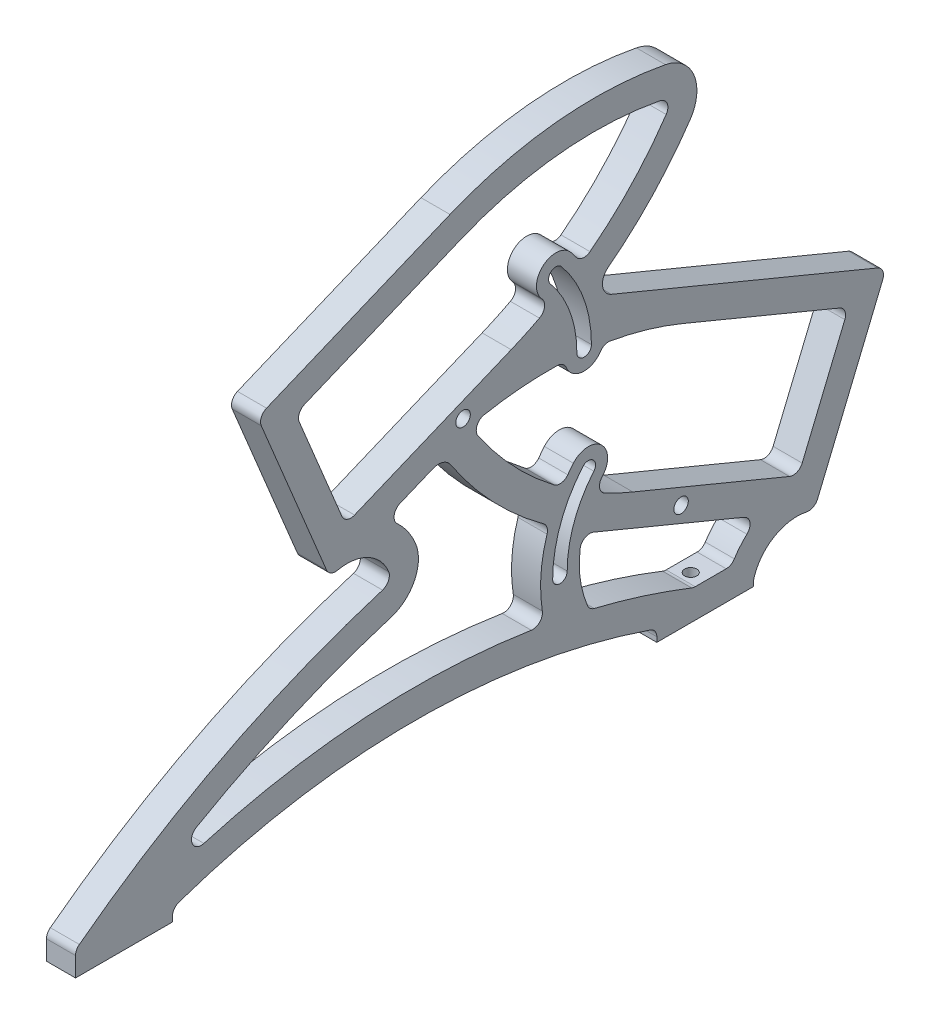
SolidWorks part; units mm, degrees
material "1060 Alloy"
ref_plane "Front Plane" through (0, 0, 0) normal (0, 0, 1) x (1, 0, 0)
ref_plane "Top Plane" through (0, 0, 0) normal (0, 1, 0) x (1, 0, 0)
ref_plane "Right Plane" through (0, 0, 0) normal (1, 0, 0) x (0, 0, -1)
sketch "Sketch1" plane through (0, 0, 0) normal (1, 0, 0) x (0, 0, -1)
  line L0 (0, 0) -> (0, 5)
  line L1 (38.8897, 80.8553) -> (54.5797, 42.9762) construction
  line L2 (38.8897, 80.8553) -> (112.8001, 111.47) construction
  line L3 (54.5797, 42.9762) -> (128.4901, 73.5909) construction
  line L4 (41.5028, 79.7729) -> (54.1314, 49.2849) construction
  line L5 (112.8001, 111.47) -> (128.4901, 73.5909) construction
  line L6 (20, 1) -> (20, 0)
  line L7 (0, 0) -> (20, 0)
  line L8 (54.1314, 49.2849) -> (91.0866, 64.5922) construction
  line L9 (78.458, 95.0802) -> (41.5028, 79.7729) construction
  line L10 (80, 60) -> (105, 60) construction
  line L11 (99.1511, 76.0697) -> (80, 60) construction
  line L12 (100, 22) -> (125, 22) construction
  line L13 (125, 22) -> (105.8489, 38.0697) construction
  line L14 (166.1103, 42.8553) -> (150.4203, 4.9762) construction
  line L15 (166.1103, 42.8553) -> (92.1999, 73.47) construction
  line L16 (150.4203, 4.9762) -> (76.5099, 35.5909) construction
  line L17 (92.1999, 73.47) -> (76.5099, 35.5909) construction
  line L18 (150.8686, 11.2849) -> (163.4972, 41.7729) construction
  line L19 (163.4972, 41.7729) -> (126.542, 57.0802) construction
  line L20 (113.9134, 26.5922) -> (150.8686, 11.2849) construction
  line L21 (157.1829, 26.5289) -> (85.1203, 56.3782) construction
  line L22 (47.8171, 64.5289) -> (119.8797, 94.3782) construction
  line L23 (152.4922, 7.3652) -> (167.4169, 43.3965)
  line L24 (167.4169, 43.3965) -> (110.6328, 66.9172)
  line L25 (77.31, 97.8519) -> (37.5831, 81.3965)
  line L26 (37.5831, 81.3965) -> (52.5078, 45.3652)
  line L27 (63.7245, 50.0113) -> (73.7782, 54.1757)
  line L28 (140, 0) -> (140, 1)
  line L29 (152.4922, 7.3652) -> (143.6238, 11.0386) construction
  line L30 (89.9385, 67.3638) -> (55.755, 53.2046)
  line L31 (55.755, 53.2046) -> (45.4225, 78.1493)
  line L32 (45.4225, 78.1493) -> (79.6061, 92.3086)
  line L33 (115.0615, 29.3638) -> (149.245, 15.2046)
  line L34 (149.245, 15.2046) -> (159.5775, 40.1493)
  line L35 (159.5775, 40.1493) -> (125.3939, 54.3086)
  line L36 (56.0604, 36.7884) -> (62.7895, 39.5756) construction
  line L37 (52.5078, 45.3652) -> (58.8317, 47.9846) construction
  line L38 (104.6495, 27.1823) -> (141.2755, 12.0113)
  line L39 (135.4645, 6) -> (127.5413, 6)
  line L43 (140, 0) -> (120, 0)
  line L56 (120, 1) -> (120, 0)
  line L63 (174.6584, 100) -> (-14.1241, 100) construction
  circle A0 centre (80, 60) radius 1.5
  circle A1 centre (125, 22) radius 1.5
  arc A2 (99.1511, 76.0697) -> (105, 60) centre (80, 60) cw construction
  arc A3 (106.5, 60) -> (100.3002, 77.0339) centre (80, 60) ccw
  arc A4 (103.5, 60) -> (98.002, 75.1055) centre (80, 60) ccw
  arc A5 (103.5, 60) -> (106.5, 60) centre (105, 60) ccw
  arc A6 (100.3002, 77.0339) -> (98.002, 75.1055) centre (99.1511, 76.0697) ccw
  arc A7 (105.8489, 38.0697) -> (100, 22) centre (125, 22) ccw construction
  arc A8 (104.6998, 39.0339) -> (98.5, 22) centre (125, 22) ccw
  arc A9 (106.998, 37.1055) -> (101.5, 22) centre (125, 22) ccw
  arc A10 (106.998, 37.1055) -> (104.6998, 39.0339) centre (105.8489, 38.0697) ccw
  arc A11 (98.5, 22) -> (101.5, 22) centre (100, 22) ccw
  arc A12 (91.0866, 64.5922) -> (124.4152, 91.7344) centre (62.3973, 133.8542) ccw construction
  arc A13 (124.4152, 91.7344) -> (121.2174, 99.4547) centre (120.279, 94.5436) ccw construction
  arc A14 (121.2174, 99.4547) -> (78.458, 95.0802) centre (107.1473, 25.8182) ccw construction
  arc A15 (126.542, 57.0802) -> (83.7826, 61.4547) centre (97.8527, -12.1818) ccw construction
  arc A16 (83.7826, 61.4547) -> (80.5848, 53.7344) centre (84.721, 56.5436) ccw construction
  arc A17 (80.5848, 53.7344) -> (113.9134, 26.5922) centre (142.6027, 95.8542) ccw construction
  arc A18 (109.9511, 72.0663) -> (110.6328, 66.9172) centre (111.7808, 69.6889) ccw
  arc A19 (109.9511, 72.0663) -> (126.897, 90.0489) centre (62.3973, 133.8542) ccw
  arc A20 (126.897, 90.0489) -> (121.7804, 102.4014) centre (120.279, 94.5436) ccw
  arc A21 (121.7804, 102.4014) -> (77.31, 97.8519) centre (107.1473, 25.8182) ccw
  arc A22 (73.7782, 54.1757) -> (77.4337, 53.051) centre (74.9262, 51.404) cw
  arc A23 (77.4337, 53.051) -> (97.7957, 32.0463) centre (142.6027, 95.8542) ccw
  arc A24 (152.4922, 7.3652) -> (140.0944, 1.6073) centre (148.9396, -1.2116) ccw
  arc A25 (140.0944, 1.6073) -> (140, 1) centre (142, 1) ccw
  arc A26 (20, 1) -> (21.3514, 2.8919) centre (22, 1) cw
  arc A27 (52.5078, 45.3652) -> (64.6372, 40.341) centre (56.0604, 36.7884) cw
  arc A28 (79.6061, 92.3086) -> (120.6543, 96.508) centre (107.1473, 25.8182) cw
  arc A29 (120.6543, 96.508) -> (121.9335, 93.4199) centre (120.279, 94.5436) cw
  arc A30 (121.9335, 93.4199) -> (104.5131, 75.4954) centre (62.3973, 133.8542) cw
  arc A31 (104.5131, 75.4954) -> (102.2153, 78.6408) centre (80, 60) ccw
  arc A32 (102.2153, 78.6408) -> (96.0869, 73.4985) centre (99.1511, 76.0697) ccw
  arc A33 (96.0869, 73.4985) -> (97.7756, 71.1816) centre (80, 60) cw
  arc A34 (97.7756, 71.1816) -> (89.9385, 67.3638) centre (62.3973, 133.8542) cw
  arc A35 (125.3939, 54.3086) -> (108.8572, 58.9406) centre (97.8527, -12.1818) ccw
  arc A36 (101.01, 59.7176) -> (84.3457, 58.508) centre (97.8527, -12.1818) ccw
  arc A37 (84.3457, 58.508) -> (83.0665, 55.4199) centre (84.721, 56.5436) ccw
  arc A38 (83.0665, 55.4199) -> (100.4869, 37.4954) centre (142.6027, 95.8542) ccw
  arc A39 (101.01, 59.7176) -> (108.8572, 58.9406) centre (105, 60) ccw
  arc A40 (100.4869, 37.4954) -> (102.7847, 40.6408) centre (125, 22) cw
  arc A41 (102.7847, 40.6408) -> (108.9131, 35.4985) centre (105.8489, 38.0697) cw
  arc A42 (107.2244, 33.1816) -> (115.0615, 29.3638) centre (142.6027, 95.8542) ccw
  arc A43 (108.9131, 35.4985) -> (107.2244, 33.1816) centre (125, 22) ccw
  arc A44 (120, 1) -> (118.6486, 2.8919) centre (118, 1) ccw
  arc A45 (118.6486, 2.8919) -> (21.3514, 2.8919) centre (70, -139) ccw
  arc A46 (64.6372, 40.341) -> (63.3742, 37.663) centre (62.7895, 39.5756) cw
  arc A47 (63.3742, 37.663) -> (0, 5) centre (121.846, -153.5987) ccw
  arc A48 (97.7957, 32.0463) -> (96.9455, 14.6553) centre (125, 22) ccw
  arc A49 (96.9455, 14.6553) -> (10.2958, 5.1229) centre (70, -139) ccw
  arc A50 (10.2958, 5.1229) -> (65.1284, 31.9252) centre (121.846, -153.5987) cw
  arc A51 (63.7245, 50.0113) -> (70.1805, 42.6371) centre (56.0604, 36.7884) cw
  arc A52 (65.1284, 31.9252) -> (70.1805, 42.6371) centre (62.7895, 39.5756) ccw
  arc A53 (104.6495, 27.1823) -> (106.1445, 12.755) centre (125, 22) ccw
  arc A54 (106.1445, 12.755) -> (127.5413, 6) centre (70, -139) cw
  arc A55 (141.2755, 12.0113) -> (135.4645, 6) centre (148.9396, -1.2116) ccw
  point P17 (103.4923, 68.5505)
  point P22 (101.5077, 30.5505)
  dimension "D1" = 3
  dimension "D3" = 1.5
  dimension "D8" = 5
  dimension "D11" = 22
  dimension "D12" = 80
  dimension "D14" = 22.5
  dimension "D16" = 2
  dimension "D17" = 6
  dimension "D21" = 30
  dimension "D22" = 35
  dimension "D23" = 80
  dimension "D24" = 2
  dimension "D18" = 6
  dimension "D29" = 60
  dimension "D25" = 5
  dimension "D28" = 2
  dimension "D36" = 3
  dimension "D37" = 3
  dimension "D38" = 3
  dimension "D39" = 3
  dimension "D40" = 3
  dimension "D45" = 3
  dimension "D46" = 3
  dimension "D47" = 4
  dimension "D48" = 4
  dimension "D49" = 3
  dimension "D52" = 3
  dimension "D53" = 4
  dimension "D54" = 4
  dimension "D55" = 4
  dimension "D56" = 2
  dimension "D57" = 150
  dimension "D58" = 2
  dimension "D59" = 200
  dimension "D60" = 6
  dimension "D61" = 6
  dimension "D62" = 4
  dimension "D63" = 6
  dimension "D64" = 8
  dimension "D67" = 4
  dimension "D68" = 6
  dimension "D69" = 6
  dimension "D2" = 25
  dimension "D4" = 25
  dimension "D5" = 40
  dimension "D6" = 40
  dimension "D7" = 125
  dimension "D9" = 20
  dimension "D10" = 100
  dimension "D13" = 1
  dimension "D15" = 22.5
  dimension "D19" = 40
  dimension "D20" = 30
  dimension "D26" = 2
  dimension "D27" = 2
  dimension "D30" = 3
  dimension "D31" = 3
  dimension "D32" = 100
  dimension "D33" = 3
  dimension "D34" = 3
  dimension "D35" = 3
  dimension "D41" = 3
  dimension "D42" = 3
  dimension "D43" = 3
  dimension "D44" = 3
  dimension "D50" = 3
  dimension "D51" = 3
  dimension "D65" = 6
  dimension "D66" = 3
extrude "Boss-Extrude1" add sketch "Sketch1" along normal blind 6
fillet "Fillet1" radius 2 24 edges at (3, 14.6553, -96.9455) (3, 32.0463, -97.7957) (3, 27.1823, -104.6495) (3, 12.755, -106.1445) (3, 12.0113, -141.2755) (3, 6, -135.4645) (3, 6, -127.5413) (3, 37.4954, -100.4869) (3, 33.1816, -107.2244) (3, 15.2046, -149.245) (3, 40.1493, -159.5775) (3, 43.3965, -167.4169) (3, 7.3652, -152.4922) (3, 75.4954, -104.5131) (3, 71.1816, -97.7756) (3, 53.2046, -55.755) (3, 81.3965, -37.5831) (3, 78.1493, -45.4225) (3, 45.3652, -52.5078) (3, 50.0113, -63.7245) (3, 5.1229, -10.2958) (3, 5, 0) (3, 58.9406, -108.8572) (3, 59.7176, -101.01)
hole_wizard "Tap Drill for M3 Tap1" positions "Sketch3" profile "Sketch2" hole size "M3" standard "ISO"
sketch "Sketch3" plane through (0, 0, 0) normal (0, -1, 0) x (-1, 0, 0)
  line L0 (-6, 20) -> (0, 20) construction
  line L1 (0, 0) -> (0, 20) construction
  line L2 (-6, 120) -> (0, 120) construction
  point P0 (-3, 10)
  point P2 (-3, 130)
  dimension "D1" = 10
  dimension "D2" = 3
  dimension "D3" = 10
sketch "Sketch2" plane through (3, 0, -10) normal (1, 0, 0) x (0, 0, -1)
  line L0 (0, 0) -> (0, 10.7511)
  line L1 (0, 10.7511) -> (1.25, 10)
  line L2 (1.25, 10) -> (1.25, 0)
  line L5 (1.25, 0) -> (0, 0)
  line L10 (0, 10.7511) -> (-1.25, 10) construction
  line L11 (0, -6.35) -> (0, 107.95) construction
  dimension "Hole Dia." = 2.5
  dimension "Hole Depth" = 10
  dimension "Drill Angle" = 118
equation "\"ˇ35\"=76.24"
